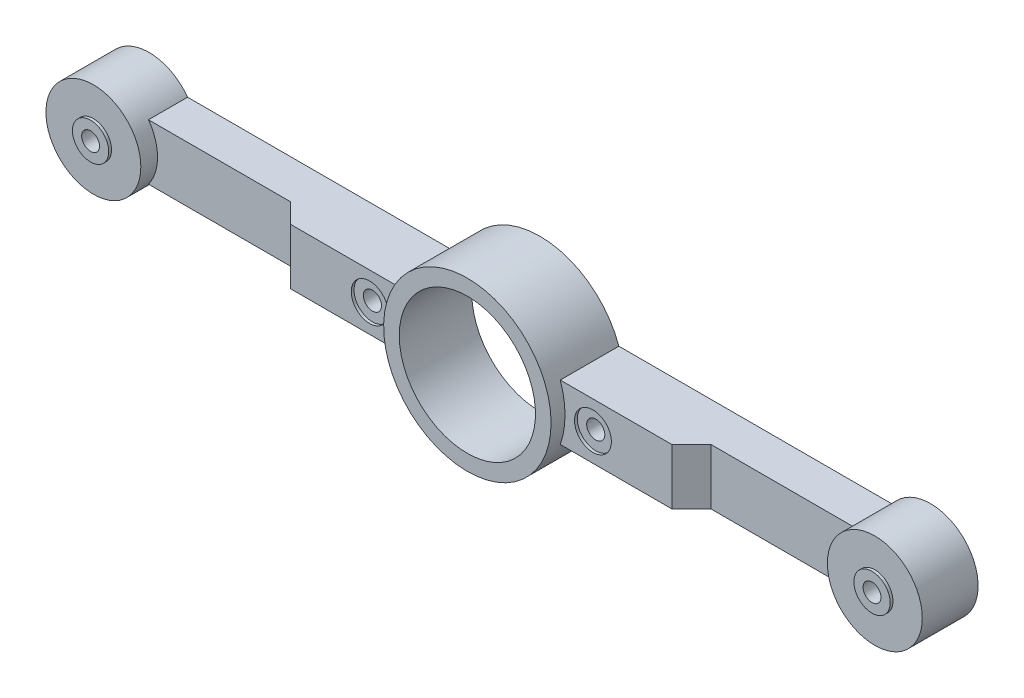
SolidWorks part; units mm, degrees
ref_plane "Front Plane" through (0, 0, 0) normal (0, 0, 1) x (1, 0, 0)
ref_plane "Top Plane" through (0, 0, 0) normal (0, 1, 0) x (1, 0, 0)
ref_plane "Right Plane" through (0, 0, 0) normal (1, 0, 0) x (0, 0, -1)
sketch "Sketch2" plane through (0, 0, 0) normal (0, 0, 1) x (1, 0, 0)
  line L1 (0, 0) -> (70, 0) construction
  line L10 (0, 5) -> (70, 5) construction
  line L12 (0, 12) -> (0, -12) construction
  line L13 (14.1421, 5) -> (63.1261, 5)
  line L15 (14.1421, -5) -> (63.1261, -5)
  line L16 (-14.1421, 5) -> (-63.1261, 5)
  line L17 (-14.1421, -5) -> (-63.1261, -5)
  circle A4 centre (70, 0) radius 2.5 construction
  circle A8 centre (0, 0) radius 15 construction
  circle A9 centre (70, 0) radius 8.5 construction
  circle A10 centre (0, 0) radius 12
  arc A12 (14.1421, 5) -> (-14.1421, 5) centre (0, 0) ccw
  arc A13 (63.1261, 5) -> (63.1261, -5) centre (70, 0) cw
  arc A14 (14.1421, -5) -> (-14.1421, -5) centre (0, 0) cw
  arc A15 (-63.1261, 5) -> (-63.1261, -5) centre (-70, 0) ccw
  dimension "D1" = 70
  dimension "D2" = 5
  dimension "D3" = 30
  dimension "D5" = 17
  dimension "D6" = 24
  dimension "D4" = 5
extrude "Boss-Extrude1" add sketch "Sketch2" along normal blind 3
sketch "Sketch3" plane through (0, 0, 0) normal (0, 0, 1) x (1, 0, 0)
  circle A0 centre (0, 0) radius 12
  circle A1 centre (0, 0) radius 15
extrude "Boss-Extrude2" add sketch "Sketch3" along normal blind 9
sketch "Sketch6" plane through (0, 0, 0) normal (0, 0, 1) x (1, 0, 0)
  circle A0 centre (-70, 0) radius 8.5
  circle A1 centre (70, 0) radius 8.5
extrude "Boss-Extrude5" add sketch "Sketch6" along normal blind 3 from surface starting at face at (42.6921, 0, 3)
sketch "Sketch8" plane through (0, 0, 0) normal (0, 0, 1) x (1, 0, 0)
  line L0 (-14.1421, 5) -> (-63.1261, 5) construction
  line L1 (-34.1421, 5) -> (-14.1421, 5)
  line L2 (-34.1421, 5) -> (-34.1421, -5)
  line L3 (-34.1421, -5) -> (-14.1421, -5)
  line L4 (-14.1421, 5) -> (-14.1421, -5)
  line L5 (0, 12) -> (0, -12) construction
  line L6 (14.1421, 5) -> (14.1421, -5)
  line L7 (34.1421, -5) -> (14.1421, -5)
  line L8 (34.1421, 5) -> (34.1421, -5)
  line L9 (34.1421, 5) -> (14.1421, 5)
  circle A0 centre (0, 0) radius 12 construction
  dimension "D1" = 20
extrude "Boss-Extrude6" add sketch "Sketch8" along normal blind 3.5 from surface starting at face at (38.4421, 0, 3)
chamfer "Chamfer2" distance 3.5 angle 45 2 edges at (-34.1421, 0, 3) (34.1421, 0, 3)
sketch "Sketch14" plane through (0, 0, 0) normal (0, 0, 1) x (1, 0, 0)
  line L1 (0, 0) -> (70, 0) construction
  line L10 (0, 5) -> (70, 5) construction
  line L12 (0, 12) -> (0, -12) construction
  line L13 (14.1421, 5) -> (63.1261, 5)
  line L15 (14.1421, -5) -> (63.1261, -5)
  line L16 (-14.1421, 5) -> (-63.1261, 5)
  line L17 (-14.1421, -5) -> (-63.1261, -5)
  circle A4 centre (70, 0) radius 2.5 construction
  circle A8 centre (0, 0) radius 15 construction
  circle A9 centre (70, 0) radius 8.5 construction
  circle A10 centre (0, 0) radius 12
  arc A12 (14.1421, 5) -> (-14.1421, 5) centre (0, 0) ccw
  arc A13 (63.1261, 5) -> (63.1261, -5) centre (70, 0) cw
  arc A14 (14.1421, -5) -> (-14.1421, -5) centre (0, 0) cw
  arc A15 (-63.1261, 5) -> (-63.1261, -5) centre (-70, 0) ccw
  dimension "D1" = 70
  dimension "D2" = 5
  dimension "D3" = 30
  dimension "D5" = 17
  dimension "D6" = 24
  dimension "D4" = 5
extrude "Boss-Extrude8" add sketch "Sketch14" against normal blind 4 from surface starting at face at (0, 0, 0)
sketch "Sketch7" plane through (0, 0, 0) normal (0, 0, 1) x (1, 0, 0)
  line L0 (0, 0) -> (-20, 0) construction
  line L1 (0, 12) -> (0, -12) construction
  circle A0 centre (-20, 0) radius 1.625
  circle A1 centre (0, 0) radius 12 construction
  circle A2 centre (20, 0) radius 1.625
  dimension "D2" = 3.25
  dimension "D1" = 20
extrude "Cut-Extrude1" cut sketch "Sketch7" along normal through all both and the other way through all
sketch "Sketch4" plane through (0, 0, 0) normal (0, 0, 1) x (1, 0, 0)
  circle A0 centre (-70, 0) radius 1.6
  circle A1 centre (70, 0) radius 1.6
  dimension "D1" = 3.2
extrude "Cut-Extrude2" cut sketch "Sketch4" along normal through all both and the other way through all
sketch "Sketch9" plane through (0, 0, 0) normal (0, 0, 1) x (1, 0, 0)
  circle A0 centre (-20, 0) radius 3.3
  circle A1 centre (20, 0) radius 3.3
  dimension "D1" = 6.6
extrude "Cut-Extrude3" cut sketch "Sketch9" against normal blind 0.5 from surface starting at face at (-21.625, 0, 6.5)
sketch "Sketch10" plane through (0, 0, 0) normal (0, 0, 1) x (1, 0, 0)
  circle A0 centre (-70, 0) radius 3.3
  circle A1 centre (70, 0) radius 3.3
  dimension "D1" = 6.6
extrude "Cut-Extrude4" cut sketch "Sketch10" along normal blind 1 from surface starting at face at (-68.4, 0, -4)
sketch "Sketch11" plane through (0, 0, 0) normal (0, 0, 1) x (1, 0, 0)
  circle A0 centre (0, 0) radius 12.2
  dimension "D1" = 24.4
extrude "Cut-Extrude5" cut sketch "Sketch11" along normal through all both and the other way through all from surface starting at face at (-66.7, 0, -4)
sketch "Sketch12" plane through (0, 0, 0) normal (0, 0, 1) x (1, 0, 0)
  circle A0 centre (-70, 0) radius 3.25
  circle A1 centre (70, 0) radius 3.25
  circle A2 centre (70, 0) radius 1.6
  circle A3 centre (-70, 0) radius 1.6
  dimension "D1" = 6.5
extrude "Boss-Extrude7" add sketch "Sketch12" along normal blind 0.5 from surface starting at face at (71.6, 0, 6)
sketch "Sketch15" plane through (0, 0, 0) normal (0, 0, 1) x (1, 0, 0)
  circle A0 centre (-20, 0) radius 3.3
  circle A1 centre (20, 0) radius 3.3
extrude "Cut-Extrude6" cut sketch "Sketch15" along normal blind 3 from surface starting at face at (12.2, 0, -4)
